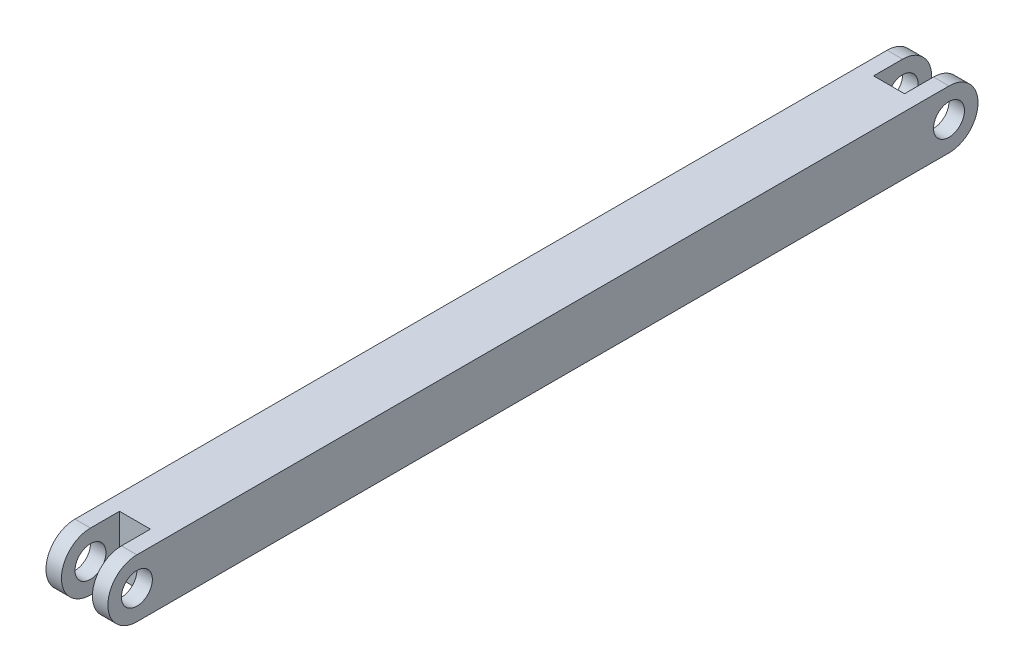
SolidWorks part; units mm, degrees
material "ABS"
ref_plane "前视基准面" through (0, 0, 0) normal (0, 0, 1) x (1, 0, 0)
ref_plane "上视基准面" through (0, 0, 0) normal (0, 1, 0) x (1, 0, 0)
ref_plane "右视基准面" through (0, 0, 0) normal (1, 0, 0) x (0, 0, -1)
sketch "草图2" plane through (0, 0, 0) normal (1, 0, 0) x (0, 0, -1)
  line L0 (-105, 7.5) -> (-105, -7.5) construction
  line L1 (-105, -7.5) -> (105, -7.5)
  line L3 (-105, 7.5) -> (105, 7.5)
  line L5 (-105, -7.5) -> (105, 7.5) construction
  line L6 (-105, 7.5) -> (105, -7.5) construction
  line L7 (105, 7.5) -> (105, -7.5) construction
  arc A0 (-105, 7.5) -> (-105, -7.5) centre (-105, 0) ccw
  arc A1 (105, 7.5) -> (105, -7.5) centre (105, 0) cw
  point P0 (0, 0)
  point P7 (0, 0)
  point P9 (0, 0)
  point P10 (0, 0)
  dimension "D1" = 15
  dimension "D2" = 210
extrude "凸台-拉伸1" add sketch "草图2" along normal blind 16
sketch "草图3" plane through (0, 7.5, 0) normal (0, 1, 0) x (1, 0, 0)
  line L1 (4, -112.5) -> (4, -97.5)
  line L2 (0, -112.5) -> (16, -112.5) construction
  line L3 (4, -97.5) -> (12, -97.5)
  line L4 (12, -97.5) -> (12, -112.5)
  line L5 (12, -112.5) -> (4, -112.5)
  line L6 (0, 105) -> (0, -105) construction
  line L7 (16, 105) -> (16, -105) construction
  line L10 (4, 112.5) -> (12, 112.5)
  line L14 (4, 112.5) -> (4, 97.5)
  line L15 (4, 97.5) -> (12, 97.5)
  line L16 (12, 97.5) -> (12, 112.5)
  line L17 (16, 105) -> (0, 105) construction
  dimension "D1" = 4
  dimension "D2" = 4
  dimension "D3" = 15
  dimension "D4" = 8
  dimension "D5" = 15
  dimension "D6" = 7.5
  dimension "D7" = 4
extrude "切除-拉伸1" cut sketch "草图3" against normal through all
sketch "草图4" plane through (16, 0, 0) normal (1, 0, 0) x (0, 0, -1)
  circle A0 centre (-105, 0) radius 4
  circle A1 centre (105, 0) radius 4
  dimension "D1" = 8
  dimension "D2" = 8
extrude "切除-拉伸2" cut sketch "草图4" against normal through all
